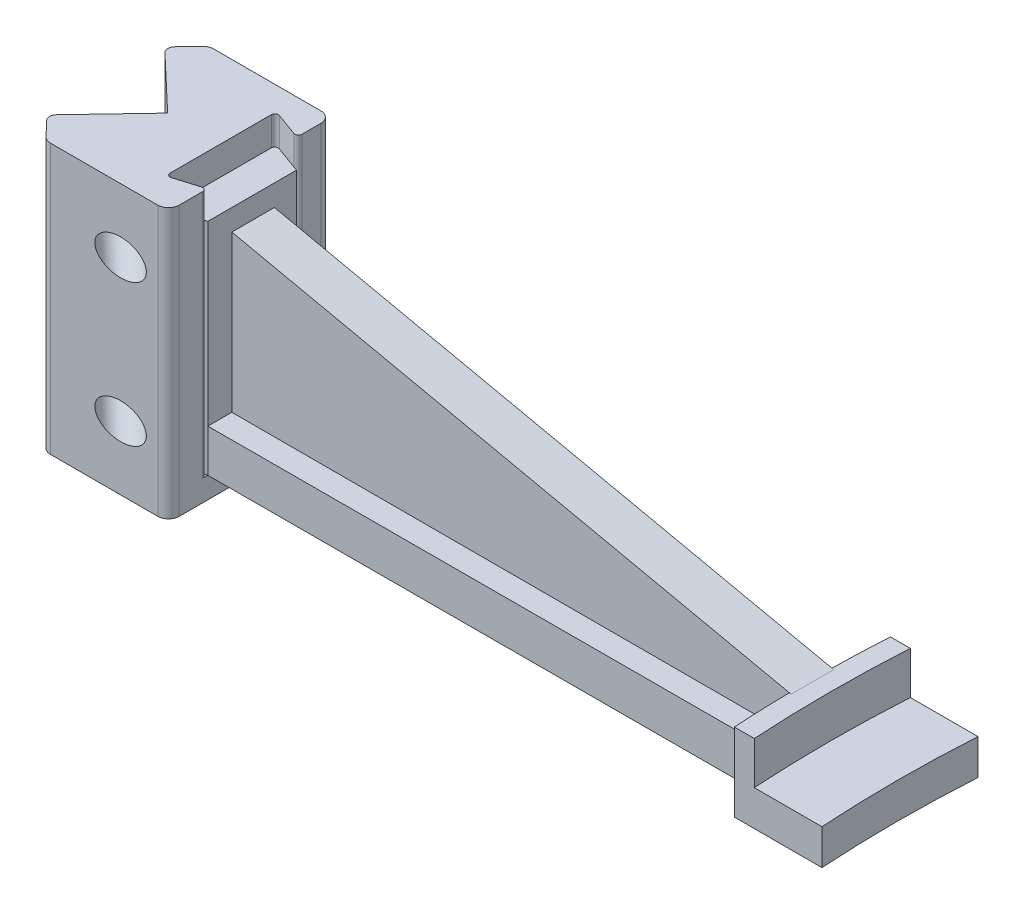
SolidWorks part; units mm, degrees
ref_plane "Front Plane" through (0, 0, 0) normal (0, 0, 1) x (1, 0, 0)
ref_plane "Top Plane" through (0, 0, 0) normal (0, 1, 0) x (1, 0, 0)
ref_plane "Right Plane" through (0, 0, 0) normal (1, 0, 0) x (0, 0, -1)
sketch "Sketch2" plane through (0, 0, 0) normal (0, 1, 0) x (1, 0, 0)
  line L0 (0, 0) -> (-181.1246, 0) construction
  line L1 (0, 0) -> (135.9511, 0) construction
  line L2 (-181.1246, 0) -> (-197.6966, 15.7434)
  line L3 (-197.6966, 15.7434) -> (-191.6108, 22.1496)
  line L4 (-191.6108, 22.1496) -> (-181.1246, 12.1877)
  line L5 (-181.1246, 12.1877) -> (-181.1246, 0)
  line L14 (0.6536, 22) -> (25.3402, 22)
  line L15 (0.6536, -22) -> (25.3402, -22)
  line L16 (25.3402, 22) -> (25.3402, -22) construction
  line L34 (-181.1246, 0) -> (-197.6966, -17.4443)
  line L49 (-197.6966, -17.4443) -> (-191.6108, -23.8504)
  line L50 (-191.6108, -23.8504) -> (-181.1246, -12.8123)
  line L51 (-181.1246, -12.8123) -> (-181.1246, 0)
  line L52 (-181.1246, 12.1877) -> (0.2109, 12.5)
  line L53 (-181.1246, -12.8123) -> (0.2109, -12.5)
  line L54 (0.2109, -12.5) -> (0.2109, 12.5) construction
  line L55 (-181.1246, 12.1877) -> (-181.1246, 24.2548) construction
  line L56 (-181.1246, -12.8123) -> (-181.1246, -19.1381)
  line L57 (-157.0246, 12.2292) -> (-166.0246, 15.5049)
  line L58 (-157.0246, 12.2292) -> (-157.0246, 22.1496)
  line L59 (-166.0246, 15.5049) -> (-166.0246, -15.5049)
  line L60 (-166.0246, -15.5049) -> (-157.0246, -12.7708)
  line L61 (-157.0246, -12.7708) -> (-157.0246, 12.2292)
  line L62 (-157.0246, 12.3356) -> (-166.1246, 15.6478)
  line L63 (-166.1246, 15.6478) -> (-166.1246, -15.6398)
  line L64 (-166.1246, -15.6398) -> (-157.0246, -12.8753)
  line L65 (-157.0246, -12.8753) -> (-157.0246, -23.8504)
  line L66 (-157.0246, -23.8504) -> (-191.6108, -23.8504)
  line L67 (-157.0246, 22.1496) -> (-191.6108, 22.1496)
  line L68 (-157.0246, -12.7708) -> (-157.0246, -12.8753)
  arc A0 (0.6536, 22) -> (0.6536, -22) centre (370.6, 0) ccw
  arc A1 (6.2636, 22) -> (6.2636, -22) centre (370.6, 0) ccw
  arc A2 (25.3402, 22) -> (25.3402, -22) centre (370.6, 0) ccw
  point P27 (-166.0246, 0)
  point P32 (5.6, 0)
  dimension "D2" = 365
  dimension "D3" = 5.6
  dimension "D4" = 19.04
  dimension "D7" = 25
  dimension "D5" = 133.531
  dimension "D6" = 136.469
  dimension "D8" = 25
  dimension "D9" = 44
  dimension "D10" = 70
  dimension "D11" = 9
  dimension "D12" = 90
  dimension "D13" = 0.1
  dimension "D14" = 0.1
  dimension "D15" = 0.1
  dimension "D16" = 90
  dimension "D17" = 15
  dimension "D18" = 46
  dimension "D19" = 186.7246
extrude "Boss-Extrude2" add sketch "Sketch2" against normal blind 12 contours A0 L52 L61 L53 | L53 L61 L52 L59 | L59 L60 L53 | L57 L59 L52 | A1 L14 A0 L15 region at (-163.0246, 0, -13.3159) region at (-161.5246, 0, 0.2785) region at (-163.0246, 0, 13.6873) region at (-78.4771, 0, 0.1355) region at (3.0196, 0, 0)
extrude "Boss-Extrude3" add sketch "Sketch2<5>" along normal blind 10 from surface contours A2 L14 A1 L15 region at (15.3473, 0, 0) starting at face at (-63.2567, -12, 0.0542)
sketch "Sketch2<5>" plane through (0, 0, 0) normal (0, 1, 0) x (1, 0, 0) same geometry as "Sketch2"
extrude "Boss-Extrude4" add sketch "Sketch2<6>" along normal blind 22 from surface contours A1 L14 A0 L15 region at (3.0196, 0, 0) starting at face at (-59.445, -12, 0.0542)
sketch "Sketch2<6>" plane through (0, 0, 0) normal (0, 1, 0) x (1, 0, 0) same geometry as "Sketch2"
extrude "Boss-Extrude5" add sketch "Sketch2<7>" against normal blind 6 from surface separate body contours L5 L4 L3 L2 | L58 L67 L4 L52 L63 L62 | L63 L52 L5 L51 L53 | L50 L51 L34 L49 | L66 L65 L64 L63 L53 L50 | L68 L60 L59 L53 L63 L64 | L52 L63 L53 L59 | L53 L61 L52 L59 | L59 L60 L53 | L57 L59 L52 | L62 L63 L52 L59 L57 L58 | L66 L56 L50 region at (-188.0032, 0, -12.1717) region at (-188.0032, 0, 13.1665) region at (-173.6246, 0, 0.2994) region at (-172.3818, 0, -17.7145) region at (-172.2252, 0, 18.8639) region at (-166.0273, 0, -13.9306) region at (-166.0746, 0, 0.2864) region at (-166.0744, 0, 12.8818) region at (-163.0246, 0, -13.3159) region at (-161.5246, 0, 0.2785) region at (-163.0246, 0, 13.6873) starting at face at (-59.445, -12, 0.0542)
sketch "Sketch2<7>" plane through (0, 0, 0) normal (0, 1, 0) x (1, 0, 0) same geometry as "Sketch2"
extrude "Boss-Extrude6" add sketch "Sketch2<8>" along normal blind 70 from surface contours L66 L65 L64 L63 L53 L50 | L50 L51 L34 L49 | L5 L4 L3 L2 | L58 L67 L4 L52 L63 L62 | L63 L52 L5 L51 L53 | L66 L56 L50 region at (-188.0032, 0, -12.1717) region at (-188.0032, 0, 13.1665) region at (-173.6246, 0, 0.2994) region at (-172.3818, 0, -17.7145) region at (-172.2252, 0, 18.8639) starting at face at (-181.9698, -12, 0.7289)
sketch "Sketch2<8>" plane through (0, 0, 0) normal (0, 1, 0) x (1, 0, 0) same geometry as "Sketch2"
extrude "Boss-Extrude7" add sketch "Sketch2<9>" along normal blind 50 contours L53 L61 L52 L59 | L57 L59 L52 | L59 L60 L53 region at (-163.0246, 0, -13.3159) region at (-161.5246, 0, 0.2785) region at (-163.0246, 0, 13.6873)
sketch "Sketch2<9>" plane through (0, 0, 0) normal (0, 1, 0) x (1, 0, 0) same geometry as "Sketch2"
sketch "Sketch4" plane through (0, 0, 0) normal (0, 0, 1) x (1, 0, 0)
  line L5 (0.6536, 10) -> (-157.0246, 44)
  line L6 (-157.0246, 50) -> (-157.0246, 0) construction
  line L7 (-157.0246, 44) -> (-157.0246, 0)
  line L8 (-181.1246, 0) -> (0.2109, 0) construction
  line L9 (-157.0246, 0) -> (0.6536, 0)
  line L10 (0.6536, 0) -> (0.6536, 10)
  line L11 (0.6536, -12) -> (0.6536, 10) construction
  line L12 (0.6536, 10) -> (0, 10) construction
  dimension "D1" = 44
extrude "Boss-Extrude17" add sketch "Sketch4" along normal blind 6 and the other way blind 6
sketch "Sketch5" plane through (-95.2035, 0, -90.4433) normal (-0.725, 0, -0.6887) x (-0.6887, 0, 0.725)
  line L0 (124.7494, -18) -> (124.7494, 58) construction
  line L1 (124.7494, 58) -> (144.7494, 58)
  line L2 (124.7494, 58) -> (124.7494, -18)
  line L3 (124.7494, -18) -> (144.7494, -18)
  line L4 (144.7494, 58) -> (144.7494, -18)
  line L5 (124.7494, 58) -> (144.7494, -18) construction
  line L6 (124.7494, -18) -> (144.7494, 58) construction
  line L7 (124.7494, -18) -> (148.8105, -18) construction
  line L8 (148.8105, 58) -> (124.7494, 58) construction
  line L10 (134.7494, 40) -> (134.7494, 0) construction
  circle A0 centre (134.7494, 40) radius 5
  circle A1 centre (134.7494, 0) radius 5
  circle A2 centre (134.7494, 0) radius 2.75
  circle A3 centre (134.7494, 40) radius 2.75
  point P0 (134.7494, 20)
  point P11 (134.7494, 20)
  dimension "D2" = 5.5
  dimension "D3" = 10
  dimension "D1" = 20
  dimension "D4" = 40
extrude "Cut-Extrude1" cut sketch "Sketch5" against normal through all from offset 8 contours A0 | A1 offset against normal yes
extrude "Cut-Extrude2" cut sketch "Sketch5<3>" against normal through all both and the other way through all contours A3 | A2 region at (-188.0121, 0, 7.25) region at (-188.0121, 40, 7.25)
sketch "Sketch5<3>" plane through (-95.2035, 0, -90.4433) normal (-0.725, 0, -0.6887) x (-0.6887, 0, 0.725) same geometry as "Sketch5"
mirror "Mirror1" about plane through (0, 0, 0) normal (0, 0, 1) of "Cut-Extrude2", "Cut-Extrude1"
fillet "Fillet1" radius 1 4 edges at (-157.0246, 23, 12.8753) (-157.0246, 23, -12.3356) (-166.1246, 23, 15.6398) (-166.1246, 23, -15.6478)
fillet "Fillet2" radius 1 2 edges at (-166.0246, 19, 15.5049) (-166.0246, 19, -15.5049)
fillet "Fillet3" radius 3 4 edges at (-191.6108, 20, -22.1496) (-191.6108, 20, 23.8504) (-157.0246, 20, -22.1496) (-157.0246, 20, 23.8504)
fillet "Fillet4" radius 2 2 edges at (-197.6966, 20, -15.7434) (-197.6966, 20, 17.4443)
